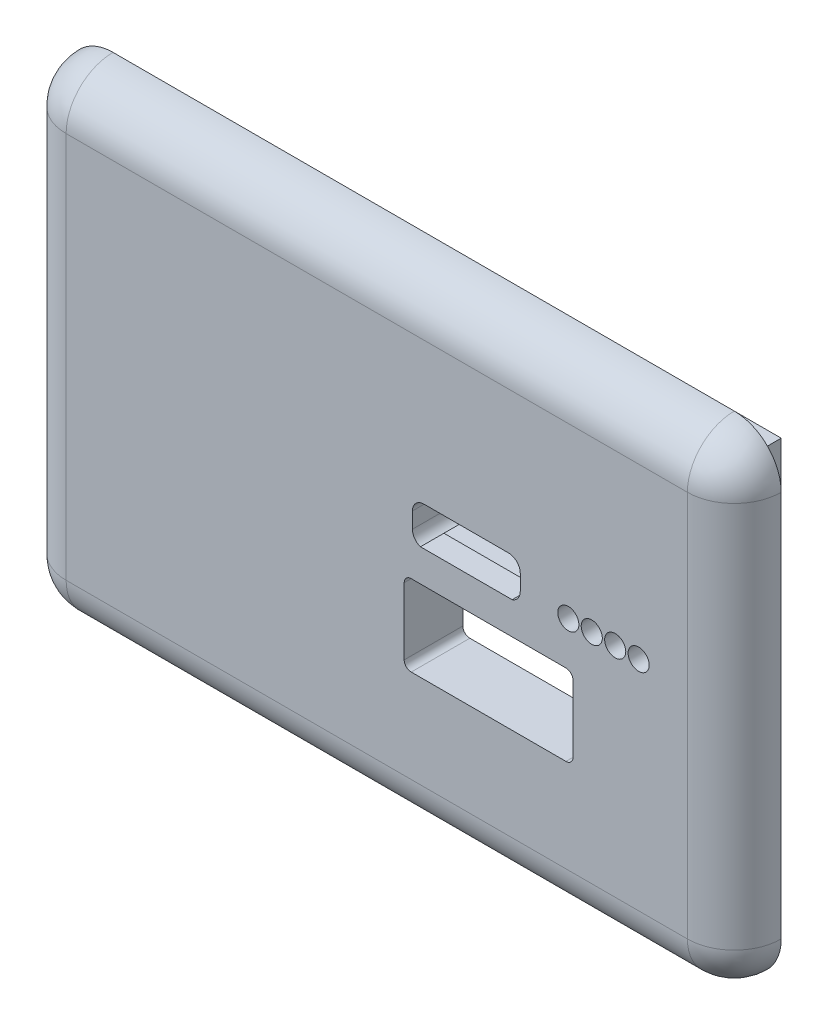
SolidWorks part; units mm, degrees
ref_plane "Plano frontal" through (0, 0, 0) normal (0, 0, 1) x (1, 0, 0)
ref_plane "Plano superior" through (0, 0, 0) normal (0, 1, 0) x (1, 0, 0)
ref_plane "Plano direito" through (0, 0, 0) normal (1, 0, 0) x (0, 0, -1)
sketch "Esboço1" plane through (0, 0, 0) normal (0, 0, 1) x (1, 0, 0)
  line L1 (4, 0) -> (57, 0)
  line L2 (0, -4) -> (0, -37)
  line L3 (4, -41) -> (57, -41)
  line L4 (61, -4) -> (61, -37)
  arc A0 (0, -37) -> (4, -41) centre (4, -37) ccw
  arc A1 (57, -41) -> (61, -37) centre (57, -37) ccw
  arc A2 (4, 0) -> (0, -4) centre (4, -4) ccw
  arc A3 (57, 0) -> (61, -4) centre (57, -4) cw
  point P7 (0, -41)
  point P12 (0, 0)
  point P15 (61, 0)
  dimension "D3" = 4
  dimension "D1" = 41
  dimension "D2" = 61
extrude "Ressalto-extrusão1" add sketch "Esboço1" along normal blind 4
sketch "Esboço3" plane through (0, 0, 4) normal (0, 0, 1) x (1, 0, 0)
  line L0 (53.69, -18.41) -> (53.69, -19.41)
  line L1 (44.84, -18.41) -> (52.84, -18.41) construction
  line L2 (43.99, -18.41) -> (43.99, -19.41)
  line L3 (47.6353, -18.11) -> (48.0447, -18.11)
  line L4 (0, -4) -> (0, -37)
  line L5 (4, -41) -> (57, -41)
  line L6 (61, -37) -> (61, -4)
  line L7 (57, 0) -> (4, 0)
  line L8 (0, -4) -> (0, -37)
  line L9 (4, -41) -> (57, -41)
  line L10 (61, -37) -> (61, -4)
  line L11 (57, 0) -> (4, 0)
  line L12 (34.54, -16.11) -> (41.74, -16.11)
  line L13 (42.0522, -19.41) -> (43.99, -19.41)
  line L14 (53.69, -19.41) -> (56.34, -19.41)
  line L15 (45.6353, -18.11) -> (46.0447, -18.11)
  line L16 (49.6353, -18.11) -> (50.0447, -18.11)
  line L17 (51.6353, -18.11) -> (52.0447, -18.11)
  line L18 (33.44, -22.16) -> (46.64, -22.16)
  line L19 (47.24, -22.76) -> (47.24, -28.46)
  line L20 (33.44, -29.06) -> (46.64, -29.06)
  line L21 (0, -4) -> (0, -37) construction
  line L22 (4, -41) -> (57, -41) construction
  line L25 (42.74, -17.11) -> (42.74, -18.46)
  line L26 (32.84, -22.76) -> (32.84, -28.46)
  line L27 (33.54, -17.11) -> (33.54, -18.46)
  line L43 (30.24, -19.41) -> (34.2278, -19.41)
  line L44 (56.34, -19.41) -> (56.34, -21.01)
  line L45 (30.24, -21.01) -> (56.34, -21.01)
  line L48 (30.24, -19.41) -> (30.24, -21.01)
  arc A0 (33.54, -18.46) -> (34.2278, -19.41) centre (34.54, -18.46) ccw
  arc A1 (42.74, -18.46) -> (42.0522, -19.41) centre (41.74, -18.46) cw
  arc A2 (41.74, -16.11) -> (42.74, -17.11) centre (41.74, -17.11) cw
  arc A3 (34.54, -16.11) -> (33.54, -17.11) centre (34.54, -17.11) ccw
  arc A4 (53.69, -18.41) -> (52.0447, -18.11) centre (52.84, -18.41) ccw
  arc A8 (46.64, -22.16) -> (47.24, -22.76) centre (46.64, -22.76) cw
  arc A9 (46.64, -29.06) -> (47.24, -28.46) centre (46.64, -28.46) ccw
  arc A10 (32.84, -28.46) -> (33.44, -29.06) centre (33.44, -28.46) ccw
  arc A11 (33.44, -22.16) -> (32.84, -22.76) centre (33.44, -22.76) ccw
  arc A12 (45.6353, -18.11) -> (43.99, -18.41) centre (44.84, -18.41) ccw
  arc A13 (47.6353, -18.11) -> (46.0447, -18.11) centre (46.84, -18.41) ccw
  arc A14 (49.6353, -18.11) -> (48.0447, -18.11) centre (48.84, -18.41) ccw
  arc A15 (51.6353, -18.11) -> (50.0447, -18.11) centre (50.84, -18.41) ccw
  arc A17 (0, -37) -> (4, -41) centre (4, -37) ccw
  arc A18 (0, -37) -> (4, -41) centre (4, -37) ccw
  arc A19 (57, -41) -> (61, -37) centre (57, -37) ccw
  arc A20 (57, -41) -> (61, -37) centre (57, -37) ccw
  arc A21 (61, -4) -> (57, 0) centre (57, -4) ccw
  arc A22 (61, -4) -> (57, 0) centre (57, -4) ccw
  arc A23 (4, 0) -> (0, -4) centre (4, -4) ccw
  arc A24 (4, 0) -> (0, -4) centre (4, -4) ccw
  point P22 (33.54, -19.46)
  point P25 (42.74, -19.46)
  point P32 (32.94, -28.96)
  point P35 (47.14, -28.96)
  point P38 (47.14, -22.26)
  dimension "D5" = 1
  dimension "D6" = 6.9
  dimension "D10" = 0.6
  dimension "D26" = 21.54
  dimension "D4" = 1
  dimension "D20" = 1.7
  dimension "D7" = 30.24
  dimension "D8" = 14.4
  dimension "D9" = 32.84
  dimension "D11" = 32.94
  dimension "D12" = 34.2278
  dimension "D13" = 3.5
  dimension "D14" = 33.54
  dimension "D15" = 42.74
  dimension "D16" = 47.14
  dimension "D17" = 12.04
  dimension "D18" = 18.74
  dimension "D19" = 24.89
  dimension "D21" = 2
  dimension "D22" = 2
  dimension "D23" = 2
  dimension "D24" = 2
  dimension "D25" = 11.94
  dimension "D27" = 19.99
  dimension "D28" = 21.59
  dimension "D31" = 0
  dimension "D33" = 56.34
  dimension "D35" = 0.3
  dimension "D1" = 0
sketch "Esboço8" plane through (0, 0, 4) normal (0, 0, 1) x (1, 0, 0)
  line L0 (34.2278, -19.41) -> (42.0522, -19.41)
  line L4 (0, -4) -> (0, -37)
  line L5 (4, -41) -> (57, -41)
  line L6 (61, -37) -> (61, -4)
  line L7 (57, 0) -> (4, 0)
  line L8 (0, -4) -> (0, -37)
  line L9 (4, -41) -> (57, -41)
  line L10 (61, -37) -> (61, -4)
  line L11 (57, 0) -> (4, 0)
  line L12 (32.84, -22.76) -> (32.84, -28.46)
  line L13 (46.64, -22.16) -> (33.44, -22.16)
  line L14 (47.24, -28.46) -> (47.24, -22.76)
  line L15 (33.44, -29.06) -> (46.64, -29.06)
  line L16 (32.84, -22.76) -> (32.84, -28.46)
  line L17 (46.64, -22.16) -> (33.44, -22.16)
  line L18 (47.24, -28.46) -> (47.24, -22.76)
  line L19 (33.44, -29.06) -> (46.64, -29.06)
  line L31 (53.69, -19.41) -> (53.69, -18.41)
  line L32 (56.34, -19.41) -> (53.69, -19.41)
  line L33 (56.34, -21.01) -> (56.34, -19.41)
  line L34 (30.24, -21.01) -> (56.34, -21.01)
  line L35 (30.24, -19.41) -> (30.24, -21.01)
  line L36 (34.2278, -19.41) -> (30.24, -19.41)
  line L37 (33.54, -17.11) -> (33.54, -18.46)
  line L38 (41.74, -16.11) -> (34.54, -16.11)
  line L39 (42.74, -18.46) -> (42.74, -17.11)
  line L40 (43.99, -19.41) -> (42.0522, -19.41)
  line L41 (43.99, -18.41) -> (43.99, -19.41)
  line L42 (46.0447, -18.11) -> (45.6353, -18.11)
  line L43 (48.0447, -18.11) -> (47.6353, -18.11)
  line L44 (50.0447, -18.11) -> (49.6353, -18.11)
  line L45 (52.0447, -18.11) -> (51.6353, -18.11)
  line L52 (33.54, -17.11) -> (33.54, -18.46)
  line L53 (41.74, -16.11) -> (34.54, -16.11)
  line L54 (42.74, -18.46) -> (42.74, -17.11)
  arc A4 (32.84, -28.46) -> (33.44, -29.06) centre (33.44, -28.46) ccw
  arc A5 (33.44, -22.16) -> (32.84, -22.76) centre (33.44, -22.76) ccw
  arc A6 (47.24, -22.76) -> (46.64, -22.16) centre (46.64, -22.76) ccw
  arc A7 (46.64, -29.06) -> (47.24, -28.46) centre (46.64, -28.46) ccw
  arc A8 (32.84, -28.46) -> (33.44, -29.06) centre (33.44, -28.46) ccw
  arc A9 (33.44, -22.16) -> (32.84, -22.76) centre (33.44, -22.76) ccw
  arc A10 (47.24, -22.76) -> (46.64, -22.16) centre (46.64, -22.76) ccw
  arc A11 (46.64, -29.06) -> (47.24, -28.46) centre (46.64, -28.46) ccw
  circle A12 centre (46.84, -18.41) radius 0.9
  circle A13 centre (48.84, -18.41) radius 0.9
  circle A14 centre (50.84, -18.41) radius 0.9
  circle A15 centre (52.84, -18.41) radius 0.9
  arc A16 (0, -37) -> (4, -41) centre (4, -37) ccw
  arc A17 (53.69, -18.41) -> (52.0447, -18.11) centre (52.84, -18.41) ccw
  arc A18 (33.54, -18.46) -> (34.2278, -19.41) centre (34.54, -18.46) ccw
  arc A19 (34.54, -16.11) -> (33.54, -17.11) centre (34.54, -17.11) ccw
  arc A20 (42.74, -17.11) -> (41.74, -16.11) centre (41.74, -17.11) ccw
  arc A21 (42.0522, -19.41) -> (42.74, -18.46) centre (41.74, -18.46) ccw
  arc A22 (45.6353, -18.11) -> (43.99, -18.41) centre (44.84, -18.41) ccw
  arc A23 (47.6353, -18.11) -> (46.0447, -18.11) centre (46.84, -18.41) ccw
  arc A24 (49.6353, -18.11) -> (48.0447, -18.11) centre (48.84, -18.41) ccw
  arc A25 (51.6353, -18.11) -> (50.0447, -18.11) centre (50.84, -18.41) ccw
  arc A26 (0, -37) -> (4, -41) centre (4, -37) ccw
  arc A27 (33.54, -18.46) -> (34.2278, -19.41) centre (34.54, -18.46) ccw
  arc A28 (34.54, -16.11) -> (33.54, -17.11) centre (34.54, -17.11) ccw
  arc A29 (42.74, -17.11) -> (41.74, -16.11) centre (41.74, -17.11) ccw
  arc A30 (42.0522, -19.41) -> (42.74, -18.46) centre (41.74, -18.46) ccw
  arc A31 (57, -41) -> (61, -37) centre (57, -37) ccw
  arc A32 (57, -41) -> (61, -37) centre (57, -37) ccw
  arc A33 (61, -4) -> (57, 0) centre (57, -4) ccw
  arc A34 (61, -4) -> (57, 0) centre (57, -4) ccw
  arc A35 (4, 0) -> (0, -4) centre (4, -4) ccw
  arc A36 (4, 0) -> (0, -4) centre (4, -4) ccw
  dimension "D1" = 0
  dimension "D2" = 0
  dimension "D3" = 0
extrude "Corte-extrusão8" cut sketch "Esboço8" against normal blind 5 flip side to cut
fillet "Filete4" radius 4 8 edges at (1.1716, -1.1716, 4) (0, -20.5, 4) (1.1716, -39.8284, 4) (30.5, -41, 4) (59.8284, -39.8284, 4) (61, -20.5, 4) (59.8284, -1.1716, 4) (30.5, 0, 4)
sketch "Esboço11" plane through (0, 0, 0) normal (0, 0, -1) x (-1, 0, 0)
  line L1 (-4, -37) -> (-57, -37)
  line L2 (-4, -37) -> (-4, -4)
  line L3 (-4, -4) -> (-57, -4)
  line L4 (-57, -37) -> (-57, -4)
  dimension "D1" = 53
  dimension "D2" = 33
extrude "Ressalto-extrusão4" add sketch "Esboço11" along normal blind 1
extrude "Corte-extrusão9" cut sketch "Esboço3" against normal blind 8 from offset 2 flip side to cut offset against normal yes
sketch "Esboço13" plane through (0, 0, -1) normal (0, 0, -1) x (-1, 0, 0)
  line L0 (-4, -37) -> (-4, -4) construction
  line L1 (-57, -4) -> (-4, -4)
  line L2 (-57, -4) -> (-57, -6)
  line L3 (-55, -6) -> (-6, -6)
  line L4 (-4, -4) -> (-4, -6)
  line L5 (-57, -37) -> (-4, -37) construction
  line L6 (-4, -4) -> (-6, -4)
  line L7 (-4, -4) -> (-4, -37)
  line L8 (-4, -37) -> (-6, -37)
  line L9 (-6, -6) -> (-6, -35)
  line L11 (-57, -37) -> (-4, -37)
  line L12 (-57, -37) -> (-57, -35)
  line L13 (-55, -35) -> (-6, -35)
  line L14 (-4, -37) -> (-4, -35)
  line L15 (-57, -4) -> (-54.5892, -4)
  line L16 (-57, -4) -> (-57, -15.993)
  line L17 (-57, -15.993) -> (-55, -15.993)
  line L18 (-55, -6) -> (-55, -15.993)
  line L19 (-57, -37) -> (-55, -37)
  line L20 (-57, -37) -> (-57, -25)
  line L21 (-57, -25) -> (-55, -25)
  line L22 (-55, -35) -> (-55, -25)
  line M36 (-4, -37) -> (-4, -4)
  line M37 (-4, -4) -> (-57, -4)
  line M38 (-57, -4) -> (-57, -37)
  line M39 (-57, -37) -> (-4, -37)
  dimension "D1" = 2
  dimension "D2" = 2
  dimension "D3" = 2
  dimension "D4" = 2
  dimension "D5" = 12
  dimension "D6" = 12
  dimension "D7" = 2
extrude "Ressalto-extrusão5" add sketch "Esboço13" along normal blind 3 contours L13 L7 L1 L3 L9 M38 M39 M36 M37 region at (55.7946, -4.6243, -1)
fillet "Filete5" radius 1 1 edges at (56, -15.993, -4)
fillet "Filete6" radius 1 1 edges at (56, -25, -4)
